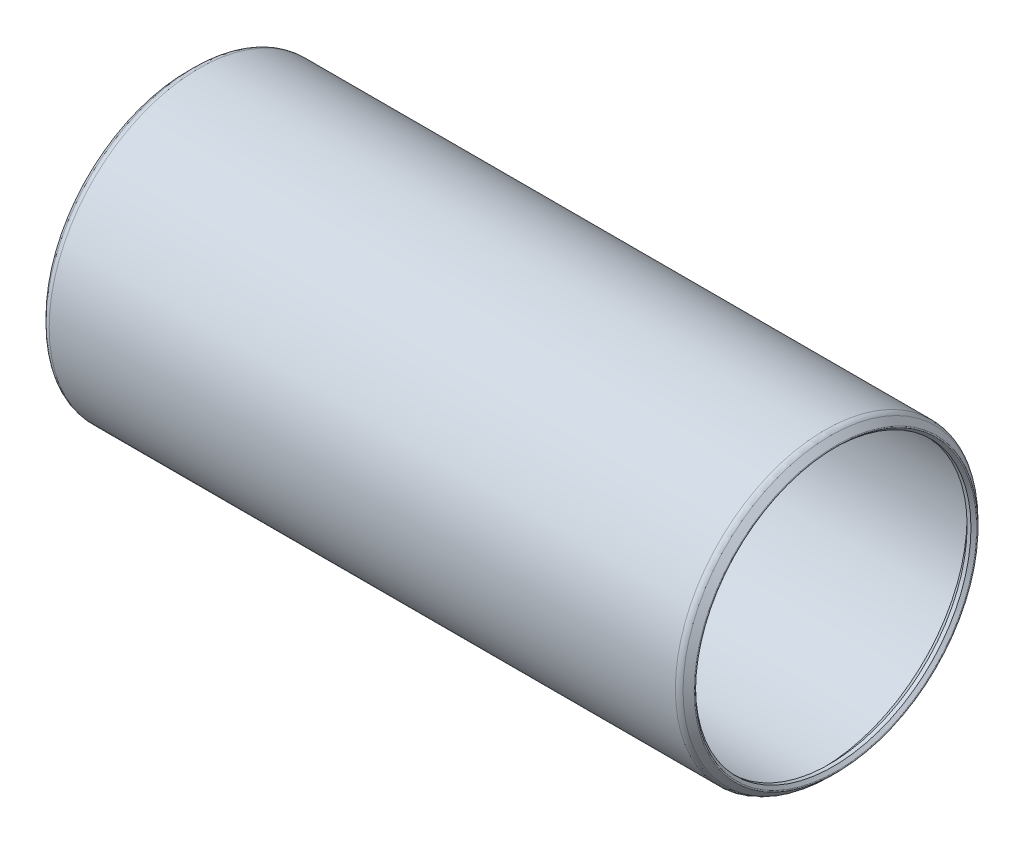
SolidWorks part; units mm, degrees
material "AISI 304"
ref_plane "Front Plane" through (0, 0, 0) normal (0, 0, 1) x (1, 0, 0)
ref_plane "Top Plane" through (0, 0, 0) normal (0, 1, 0) x (1, 0, 0)
ref_plane "Right Plane" through (0, 0, 0) normal (1, 0, 0) x (0, 0, -1)
ref_plane "Plane1" through (83.8073, 0, 0) normal (1, 0, 0) x (0, 0, -1)
sketch "Sketch1" plane through (0, 0, 0) normal (0, 0, 1) x (1, 0, 0)
  line L0 (-0.8826, 18.5547) -> (-0.508, 18.1801)
  line L1 (-0.508, 18.1801) -> (0, 18.1801)
  line L2 (0, 18.1801) -> (1.016, 19.196)
  line L3 (1.016, 19.196) -> (82.7913, 19.196)
  line L4 (82.7913, 19.196) -> (83.8073, 18.1801)
  line L5 (83.8073, 18.1801) -> (84.3153, 18.1801)
  line L6 (84.3153, 18.1801) -> (84.6899, 18.5547)
  line L7 (84.6899, 18.7343) -> (83.9542, 19.47)
  line L8 (83.2358, 19.7675) -> (0.5715, 19.7675)
  line L9 (-0.1469, 19.47) -> (-0.8826, 18.7343)
  line L10 (83.8073, 0) -> (0, 0) construction
  arc A0 (-0.8826, 18.7343) -> (-0.8826, 18.5547) centre (-0.7928, 18.6445) ccw
  arc A1 (84.6899, 18.5547) -> (84.6899, 18.7343) centre (84.6001, 18.6445) ccw
  arc A2 (83.9542, 19.47) -> (83.2358, 19.7675) centre (83.2358, 18.7515) ccw
  arc A3 (0.5715, 19.7675) -> (-0.1469, 19.47) centre (0.5715, 18.7515) ccw
revolve "Revolve1" add sketch "Sketch1" angle 360 about L10 reverse direction yes
ref_plane "Plane2" through (41.9036, 0, 0) normal (1, 0, 0) x (0, 0, -1)
ref_plane "cp1 XY" through (41.9036, 0, 0) normal (1, 0, 0) x (0, 0, -1)
ref_plane "cp1 XZ" through (0, 19.7676, 0) normal (0, -1, 0) x (-1, 0, 0)
ref_plane "cp1 YZ" through (0, 0, 0) normal (0, 0, -1) x (-1, 0, 0)
ref_axis "cp1 X" through (41.9036, 19.7676, 80.9) along (0, 0, -1)
ref_axis "cp1 Y" through (41.9036, -50, 0) along (0, 1, 0)
ref_axis "cp1 Z" through (80.9, 19.7676, 0) along (-1, 0, 0)
sketch3d "cp1"
  point P0 (41.9036, 19.7676, 0)
ref_plane "cp2 XY" through (41.9036, 0, 0) normal (1, 0, 0) x (0, 0, -1)
ref_plane "cp2 XZ" through (0, 0, 0) normal (0, -1, 0) x (-1, 0, 0)
ref_plane "cp2 YZ" through (0, 0, -19.7676) normal (0, 0, -1) x (-1, 0, 0)
ref_axis "cp2 X" through (41.9036, 0, 80.9) along (0, 0, -1)
ref_axis "cp2 Y" through (41.9036, -50, -19.7676) along (0, 1, 0)
ref_axis "cp2 Z" through (80.9, 0, -19.7676) along (-1, 0, 0)
sketch3d "cp2"
  point P0 (41.9036, 0, -19.7676)
ref_plane "cp3 XY" through (41.9036, 0, 0) normal (1, 0, 0) x (0, 0, -1)
ref_plane "cp3 XZ" through (0, -19.7676, 0) normal (0, -1, 0) x (-1, 0, 0)
ref_plane "cp3 YZ" through (0, 0, 0) normal (0, 0, -1) x (-1, 0, 0)
ref_axis "cp3 X" through (41.9036, -19.7676, 80.9) along (0, 0, -1)
ref_axis "cp3 Y" through (41.9036, -50, 0) along (0, 1, 0)
ref_axis "cp3 Z" through (80.9, -19.7676, 0) along (-1, 0, 0)
sketch3d "cp3"
  point P0 (41.9036, -19.7676, 0)
ref_plane "cp4 XY" through (41.9036, 0, 0) normal (1, 0, 0) x (0, 0, -1)
ref_plane "cp4 XZ" through (0, 0, 0) normal (0, -1, 0) x (-1, 0, 0)
ref_plane "cp4 YZ" through (0, 0, 19.7676) normal (0, 0, -1) x (-1, 0, 0)
ref_axis "cp4 X" through (41.9036, 0, 80.9) along (0, 0, -1)
ref_axis "cp4 Y" through (41.9036, -50, 19.7676) along (0, 1, 0)
ref_axis "cp4 Z" through (80.9, 0, 19.7676) along (-1, 0, 0)
sketch3d "cp4"
  point P0 (41.9036, 0, 19.7676)
ref_plane "tube_front XY" through (0, 0, 0) normal (1, 0, 0) x (0, 0, -1)
ref_plane "tube_front XZ" through (0, 0, 0) normal (0, -1, 0) x (-1, 0, 0)
ref_plane "tube_front YZ" through (0, 0, 0) normal (0, 0, -1) x (-1, 0, 0)
ref_axis "tube_front X" through (0, 0, 80.9) along (0, 0, -1)
ref_axis "tube_front Y" through (0, -50, 0) along (0, 1, 0)
ref_axis "tube_front Z" through (80.9, 0, 0) along (-1, 0, 0)
sketch3d "tube_front"
  point P0 (0, 0, 0)
ref_plane "tube_rear XY" through (83.8073, 0, 0) normal (1, 0, 0) x (0, 0, -1)
ref_plane "tube_rear XZ" through (0, 0, 0) normal (0, -1, 0) x (-1, 0, 0)
ref_plane "tube_rear YZ" through (0, 0, 0) normal (0, 0, -1) x (-1, 0, 0)
ref_axis "tube_rear X" through (83.8073, 0, 80.9) along (0, 0, -1)
ref_axis "tube_rear Y" through (83.8073, -50, 0) along (0, 1, 0)
ref_axis "tube_rear Z" through (80.9, 0, 0) along (-1, 0, 0)
sketch3d "tube_rear"
  point P0 (83.8073, 0, 0)
